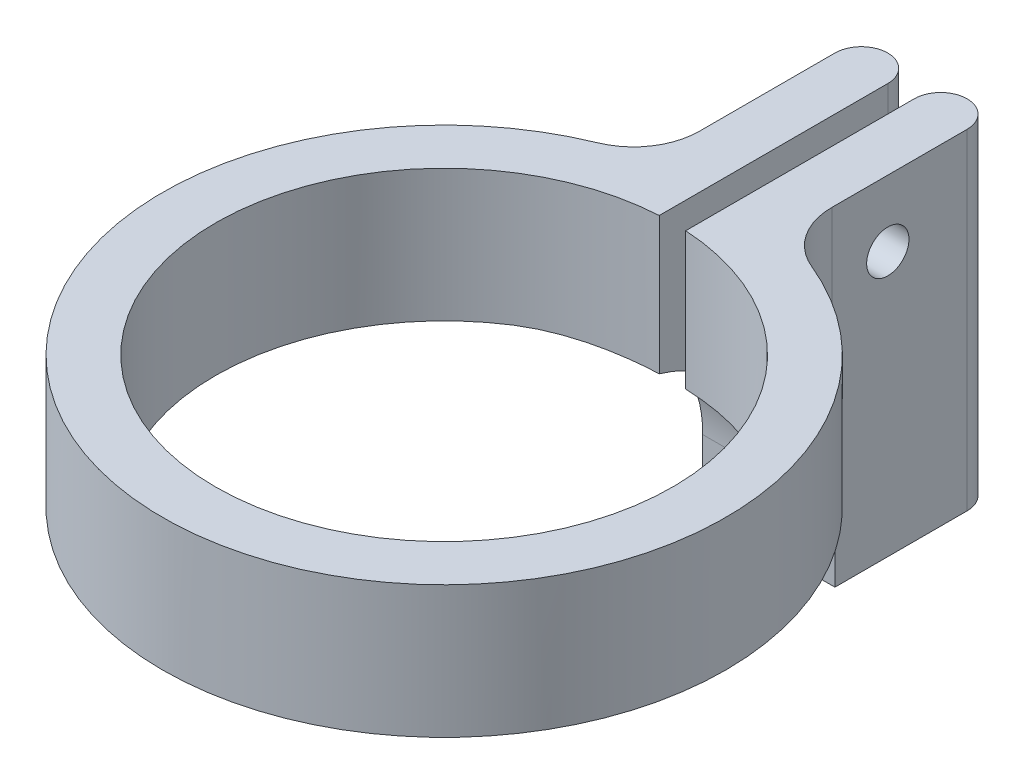
SolidWorks part; units mm, degrees
ref_plane "Front Plane" through (0, 0, 0) normal (0, 0, 1) x (1, 0, 0)
ref_plane "Top Plane" through (0, 0, 0) normal (0, 1, 0) x (1, 0, 0)
ref_plane "Right Plane" through (0, 0, 0) normal (1, 0, 0) x (0, 0, -1)
sketch "Sketch5" plane through (0, 0, 0) normal (0, 1, 0) x (1, 0, 0)
  line L1 (-1, 17.2711) -> (1, 17.2711)
  line L2 (-1, 17.2711) -> (-1, 36.5617)
  line L3 (-1, 36.5617) -> (1, 36.5617)
  line L4 (1, 17.2711) -> (1, 36.5617)
  line L5 (-5, 16.5617) -> (5, 16.5617)
  line L6 (-5, 16.5617) -> (-5, 36.5617)
  line L7 (-5, 36.5617) -> (5, 36.5617)
  line L8 (5, 16.5617) -> (5, 36.5617)
  circle A0 centre (0, 0) radius 21.3
  circle A1 centre (0, 0) radius 17.3
  point P12 (0, 0)
  point P13 (0, 36.5617)
  point P14 (0, 0)
  dimension "D1" = 34.6
  dimension "D2" = 4
  dimension "D3" = 20
  dimension "D4" = 2
  dimension "D5" = 4
extrude "Boss-Extrude4" add sketch "Sketch5" along normal blind 10 contours A1 L6 A0 L8 | A0 L2 L7 L6 | A1 L2 A0 L6 | A1 L8 A0 L4 | A0 L8 L7 L4 region at (-3.0112, 0, -19.0246) region at (3.0112, 0, -19.0246) region at (-3.0123, 0, -28.8076) region at (-10.6715, 0, 14.369) region at (3.0123, 0, -28.8076)
sketch "Sketch6" plane through (5, 0, 0) normal (1, 0, 0) x (0, 0, -1)
  line L0 (36.5617, 10) -> (36.5617, 0) construction
  circle A0 centre (28.5617, 5) radius 1.6
  point P4 (36.5617, 5)
  dimension "D1" = 3.2
  dimension "D2" = 8
extrude "Cut-Extrude2" cut sketch "Sketch6" against normal through all
fillet "Fillet4" radius 5 2 edges at (-5, 5, -20.7048) (5, 5, -20.7048)
sketch "Sketch7" plane through (0, 0, 0) normal (0, -1, 0) x (1, 0, 0)
  line L0 (1, -17.2711) -> (1, -36.5617) construction
  line L1 (-5, -36.5617) -> (-1, -36.5617)
  line L2 (-5, -36.5617) -> (-5, -24.5617)
  line L3 (-5, -24.5617) -> (-1, -24.5617)
  line L4 (-1, -36.5617) -> (-1, -24.5617)
  line L5 (5, -36.5617) -> (1, -36.5617)
  line L6 (5, -36.5617) -> (5, -24.5617)
  line L7 (5, -24.5617) -> (1, -24.5617)
  line L8 (1, -36.5617) -> (1, -24.5617)
  line L9 (-1, -17.2711) -> (-1, -36.5617) construction
  dimension "D1" = 12
extrude "Boss-Extrude5" add sketch "Sketch7" along normal blind 15
fillet "Fillet5" radius 10 2 edges at (-3, 0, -24.5617) (3, 0, -24.5617)
fillet "Fillet6" radius 2 4 edges at (5, -2.5, -36.5617) (1, -2.5, -36.5617) (-1, -2.5, -36.5617) (-5, -2.5, -36.5617)
